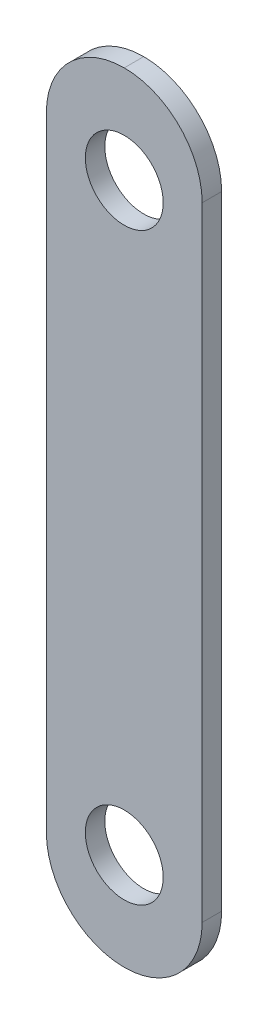
SolidWorks part; units mm, degrees
ref_plane "Front Plane" through (0, 0, 0) normal (0, 0, 1) x (1, 0, 0)
ref_plane "Top Plane" through (0, 0, 0) normal (0, 1, 0) x (1, 0, 0)
ref_plane "Right Plane" through (0, 0, 0) normal (1, 0, 0) x (0, 0, -1)
sketch "Sketch1" plane through (0, 0, 0) normal (0, 0, 1) x (1, 0, 0)
  line L2 (0, 0) -> (0, 20)
  line L3 (0, 20) -> (4, 20)
  line L4 (4, 0) -> (4, 20)
  line L5 (0, 0) -> (4, 0)
  circle A0 centre (2, 17.5) radius 1
  circle A1 centre (2, 2.5) radius 1
  dimension "D1" = 4
  dimension "D2" = 20
extrude "Boss-Extrude1" add sketch "Sketch1" along normal blind 0.5
fillet "Fillet1" radius 2 1 edges at (4, 0, 0.25)
fillet "Fillet2" radius 2 1 edges at (0, 0, 0.25)
fillet "Fillet3" radius 2 1 edges at (0, 20, 0.25)
fillet "Fillet4" radius 2 1 edges at (4, 20, 0.25)
